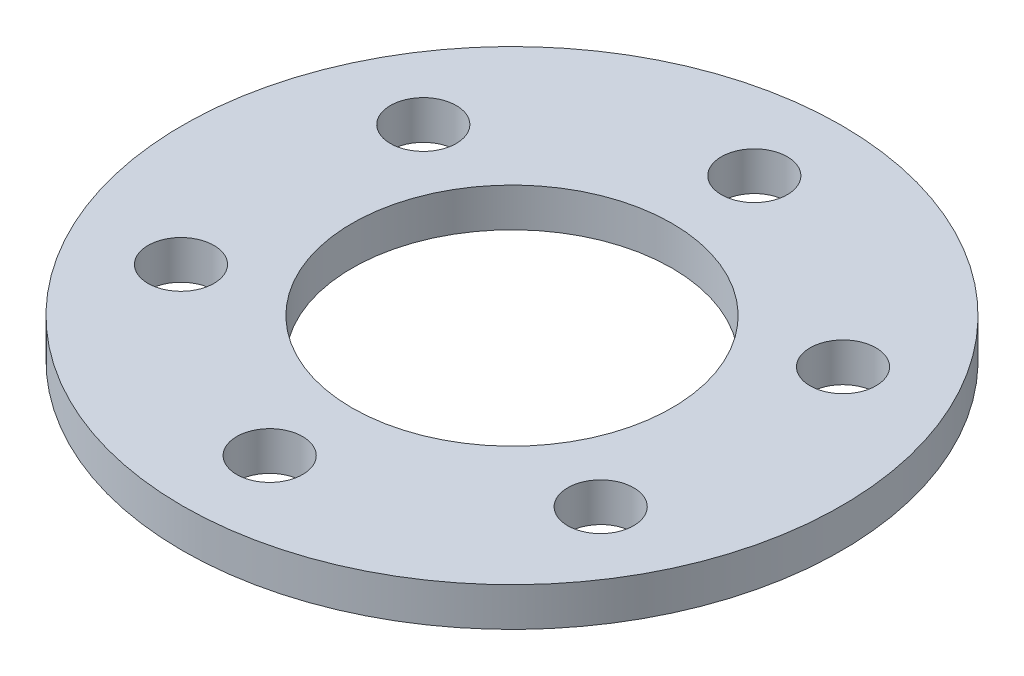
SolidWorks part; units mm, degrees
ref_plane "Front Plane" through (0, 0, 0) normal (0, 0, 1) x (1, 0, 0)
ref_plane "Top Plane" through (0, 0, 0) normal (0, 1, 0) x (1, 0, 0)
ref_plane "Right Plane" through (0, 0, 0) normal (1, 0, 0) x (0, 0, -1)
sketch "Sketch1" plane through (0, 0, 0) normal (0, 1, 0) x (1, 0, 0)
  circle A0 centre (0, 0) radius 17
  circle A1 centre (0, 0) radius 8.25
  circle A2 centre (0, 0) radius 12.5 construction
  circle A3 centre (0, 12.5) radius 1.7
  circle A6 centre (0, 0) radius 12 construction
  circle A7 centre (10.8253, 6.25) radius 1.7
  circle A8 centre (10.8253, -6.25) radius 1.7
  circle A9 centre (0, -12.5) radius 1.7
  circle A10 centre (-10.8253, -6.25) radius 1.7
  circle A11 centre (-10.8253, 6.25) radius 1.7
  point P13 (0, 0)
  point P21 (0, 0)
  dimension "D1" = 34
  dimension "D2" = 16.5
  dimension "D3" = 25
  dimension "D4" = 3.4
  dimension "D6" = 24
  dimension "D5" = 6
extrude "Boss-Extrude1" add sketch "Sketch1" along normal blind 2
